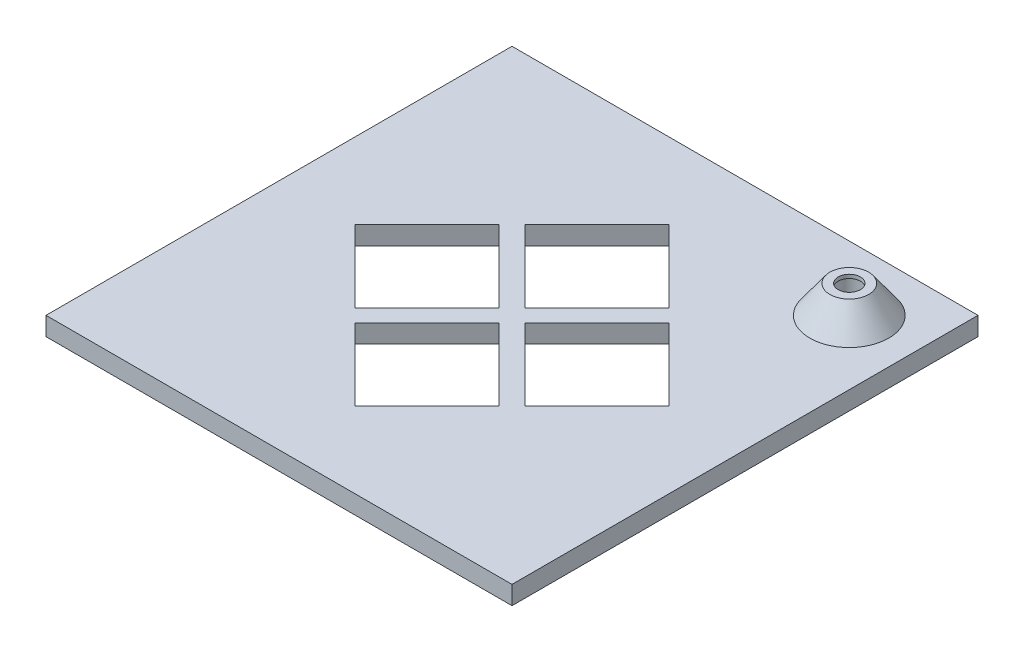
SolidWorks part; units mm, degrees
ref_plane "Front Plane" through (0, 0, 0) normal (0, 0, 1) x (1, 0, 0)
ref_plane "Top Plane" through (0, 0, 0) normal (0, 1, 0) x (1, 0, 0)
ref_plane "Right Plane" through (0, 0, 0) normal (1, 0, 0) x (0, 0, -1)
sketch "Sketch1" plane through (0, 0, 0) normal (0, 1, 0) x (1, 0, 0)
  line L1 (0, 0) -> (126, 0)
  line L2 (0, 0) -> (0, 126)
  line L3 (0, 126) -> (126, 126)
  line L4 (126, 0) -> (126, 126)
  dimension "D1" = 126
  dimension "D2" = 126
extrude "Boss-Extrude1" add sketch "Sketch1" along normal blind 5
sketch "Sketch3" plane through (0, 5, 0) normal (0, 1, 0) x (1, 0, 0)
  line L0 (108.6, 121.1) -> (108.6, 96.1) construction
  circle A0 centre (108.6, 108.6) radius 12.5
extrude "Boss-Extrude2" add sketch "Sketch3" along normal blind 7.5
sketch "Sketch4" plane through (0, 0, 0) normal (0, -1, 0) x (1, 0, 0)
  circle A1 centre (108.6, -108.6) radius 3.45
  dimension "D1" = 6.9
extrude "Cut-Extrude1" cut sketch "Sketch4" against normal blind 11.5
sketch "Sketch6" plane through (0, 12.5, 0) normal (0, 1, 0) x (1, 0, 0)
  line L0 (108.6, 121.1) -> (108.6, 96.1) construction
  circle A0 centre (108.6, 108.6) radius 12.5 construction
  circle A1 centre (108.6, 108.6) radius 3
  dimension "D1" = 6
extrude "Cut-Extrude2" cut sketch "Sketch6" against normal through all
chamfer "Chamfer1" distance 10 angle 36 1 edges at (108.6, 12.5, -96.1) first distance on face at (108.6, 12.5, -96.1)
sketch "Sketch7" plane through (0, 5, 0) normal (0, 1, 0) x (1, 0, 0)
  line L0 (63, 63) -> (63, 59.5) construction
  line L1 (66.5, 63) -> (105.5, 63) construction
  line L2 (86, 63) -> (86, 82.5) construction
  line L3 (63, 63) -> (66.5, 63) construction
  line L4 (66.5, 63) -> (86, 82.5)
  line L5 (66.5, 63) -> (86, 43.5)
  line L6 (63, 63) -> (59.5, 63) construction
  line L13 (63, 63) -> (63, 66.5) construction
  line L14 (86, 82.5) -> (105.5, 63)
  line L15 (86, 43.5) -> (105.5, 63)
  line L16 (63, 66.5) -> (63, 105.5) construction
  line L17 (63, 86) -> (82.5, 86) construction
  line L18 (63, 66.5) -> (82.5, 86)
  line L19 (63, 66.5) -> (43.5, 86)
  line L20 (82.5, 86) -> (63, 105.5)
  line L21 (43.5, 86) -> (63, 105.5)
  line L22 (59.5, 63) -> (20.5, 63) construction
  line L23 (63, 59.5) -> (63, 20.5) construction
  line L24 (40, 63) -> (40, 82.5) construction
  line L25 (63, 40) -> (43.5, 40) construction
  line L26 (59.5, 63) -> (40, 82.5)
  line L27 (59.5, 63) -> (40, 43.5)
  line L28 (40, 82.5) -> (20.5, 63)
  line L29 (40, 43.5) -> (20.5, 63)
  line L30 (63, 59.5) -> (43.5, 40)
  line L31 (63, 59.5) -> (82.5, 40)
  line L32 (43.5, 40) -> (63, 20.5)
  line L33 (82.5, 40) -> (63, 20.5)
  point P12 (63, 63)
  dimension "D3" = 3.5
  dimension "D4" = 3.5
  dimension "D5" = 3.5
  dimension "D6" = 3.5
  dimension "D7" = 39
  dimension "D9" = 39
  dimension "D11" = 39
  dimension "D12" = 39
extrude "Cut-Extrude3" cut sketch "Sketch7" against normal through all and the other way through all
